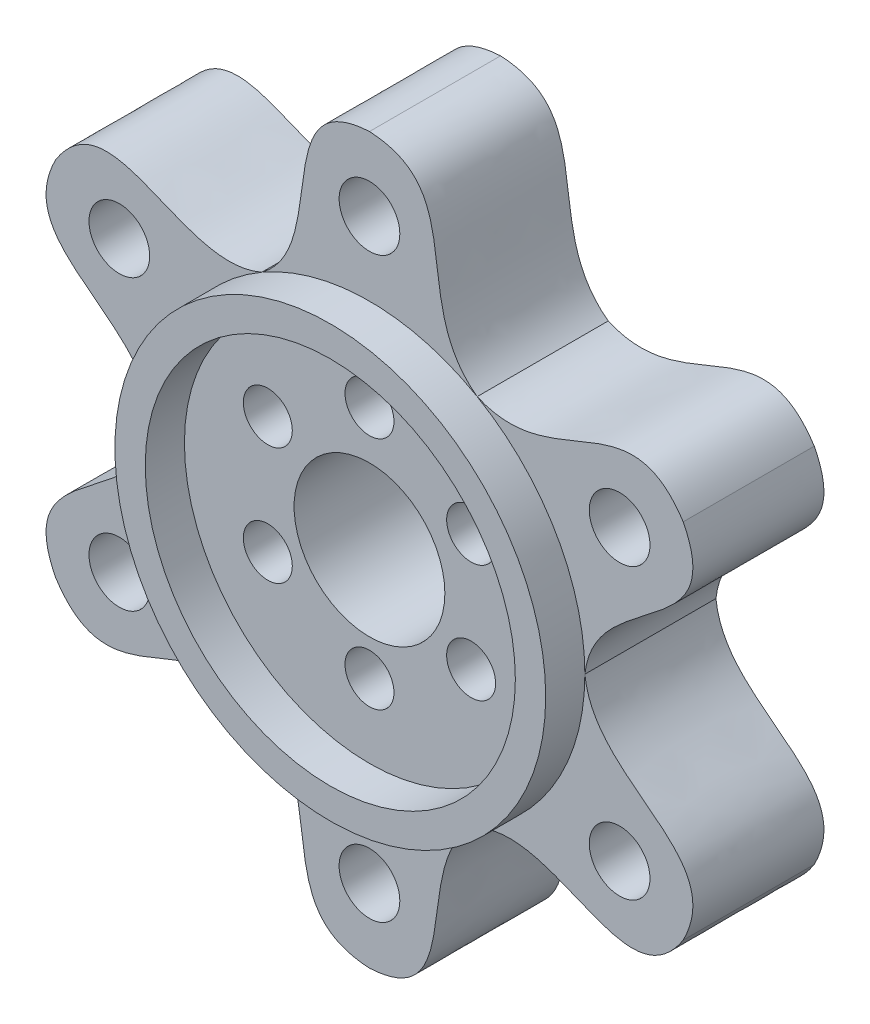
SolidWorks part; units mm, degrees
ref_plane "Front Plane" through (0, 0, 0) normal (0, 0, 1) x (1, 0, 0)
ref_plane "Top Plane" through (0, 0, 0) normal (0, 1, 0) x (1, 0, 0)
ref_plane "Right Plane" through (0, 0, 0) normal (1, 0, 0) x (0, 0, -1)
sketch "Sketch1" plane through (0, 0, 0) normal (0, 0, 1) x (1, 0, 0)
  line L0 (0, -2.035) -> (0, 2.035) construction
  line L1 (0, 0) -> (0, 46.99) construction
  circle A0 centre (0, 0) radius 9.779
  circle A1 centre (0, 0) radius 46.99
  circle A2 centre (0, 16.002) radius 3.175
  circle A3 centre (13.1849, 8.3897) radius 3.175
  circle A4 centre (13.1849, -6.8349) radius 3.175
  circle A5 centre (0, -14.4471) radius 3.175
  circle A6 centre (-13.1849, -6.8349) radius 3.175
  circle A7 centre (-13.1849, 8.3897) radius 3.175
  circle A8 centre (0, 37.465) radius 3.937
  circle A10 centre (32.4456, 18.7325) radius 3.937
  circle A11 centre (32.4456, -18.7325) radius 3.937
  circle A12 centre (0, -37.465) radius 3.937
  circle A13 centre (-32.4456, -18.7325) radius 3.937
  circle A14 centre (-32.4456, 18.7325) radius 3.937
  point P21 (0, 0.7774)
  point P36 (0, 0)
  dimension "D1" = 19.558
  dimension "D2" = 93.98
  dimension "D3" = 6.35
  dimension "D6" = 7.874
  dimension "D4" = 16.002
  dimension "D8" = 37.465
  dimension "D5" = 6
  dimension "D7" = 6
extrude "Boss-Extrude3" add sketch "Sketch1" along normal blind 17
sketch "Sketch2" plane through (0, 0, 17) normal (0, 0, 1) x (1, 0, 0)
  line L0 (0, -9.35) -> (0, 9.35) construction
  line L1 (-32.4456, 18.7325) -> (0, 37.465) construction
  line L2 (-16.2228, 28.0988) -> (-4.8895, 8.4689) construction
  line L3 (16.1678, 28.1305) -> (4.8344, 8.5004) construction
  line L6 (32.4456, -18.7325) -> (32.4456, 18.7325) construction
  line L7 (32.4456, 18.7325) -> (0, 37.465) construction
  line L8 (9.35, 0) -> (-9.35, 0) construction
  circle A0 centre (0, 0) radius 27.94 construction
  circle A1 centre (0, 0) radius 46.99 construction
  circle A2 centre (0, 0) radius 9.779 construction
  circle A3 centre (0, 0) radius 46.99
  spline S0 degree 3 poles (-13.97, 24.1967) (-4.8941, 30.8473) (-13.2477, 46.2899) (0, 46.99) knots 0 0 0 0 1 1 1 1
  spline S1 degree 3 poles (13.97, 24.1967) (4.8941, 30.8473) (13.2477, 46.2899) (0, 46.99) knots 0 0 0 0 1 1 1 1
  spline S2 degree 3 poles (-27.94, 0) (-29.1616, 11.1853) (-46.7121, 11.6721) (-40.6945, 23.495) knots 0 0 0 0 1 1 1 1
  spline S3 degree 3 poles (-13.97, 24.1967) (-24.2675, 19.6621) (-33.4643, 34.6178) (-40.6945, 23.495) knots 0 0 0 0 1 1 1 1
  spline S4 degree 3 poles (-13.97, -24.1967) (-24.2675, -19.6621) (-33.4643, -34.6178) (-40.6945, -23.495) knots 0 0 0 0 1 1 1 1
  spline S5 degree 3 poles (-27.94, 0) (-29.1616, -11.1853) (-46.7121, -11.6721) (-40.6945, -23.495) knots 0 0 0 0 1 1 1 1
  spline S6 degree 3 poles (13.97, -24.1967) (24.2675, -19.6621) (33.4643, -34.6178) (40.6945, -23.495) knots 0 0 0 0 1 1 1 1
  spline S7 degree 3 poles (27.94, 0) (29.1616, -11.1853) (46.7121, -11.6721) (40.6945, -23.495) knots 0 0 0 0 1 1 1 1
  spline S8 degree 3 poles (13.97, -24.1967) (4.8941, -30.8473) (13.2477, -46.2899) (0, -46.99) knots 0 0 0 0 1 1 1 1
  spline S9 degree 3 poles (-13.97, -24.1967) (-4.8941, -30.8473) (-13.2477, -46.2899) (0, -46.99) knots 0 0 0 0 1 1 1 1
  spline S10 degree 3 poles (27.94, 0) (29.1616, 11.1853) (46.7121, 11.6721) (40.6945, 23.495) knots 0 0 0 0 1 1 1 1
  spline S11 degree 3 poles (13.97, 24.1967) (24.2675, 19.6621) (33.4643, 34.6178) (40.6945, 23.495) knots 0 0 0 0 1 1 1 1
  point P5 (-16.2228, 28.0988)
  point P6 (16.1678, 28.1305)
  circle M8 centre (0, 0) radius 46.99
  dimension "D1" = 55.88
  dimension "D2" = 18.796
extrude "Cut-Extrude1" cut sketch "Sketch2" against normal blind 22.86 contours S1 S11 M8 | S5 S2 A3 | S10 S7 A3 | S6 S8 A3 | S9 S4 M8 | S3 S0 M8 region at (39.1487, 0, 17) region at (19.5743, 33.9037, 17) region at (19.5743, -33.9037, 17) region at (-19.5743, 33.9037, 17) region at (-19.5743, -33.9037, 17) region at (-39.1487, 0, 17)
sketch "Sketch4" plane through (0, 0, 17) normal (0, 0, 1) x (1, 0, 0)
  circle A0 centre (0, 0) radius 27.94 construction
  circle A1 centre (0, 0) radius 27.94
  circle A2 centre (0, 0) radius 24.003
  dimension "D1" = 48.006
extrude "Boss-Extrude4" add sketch "Sketch4" along normal blind 5.08
